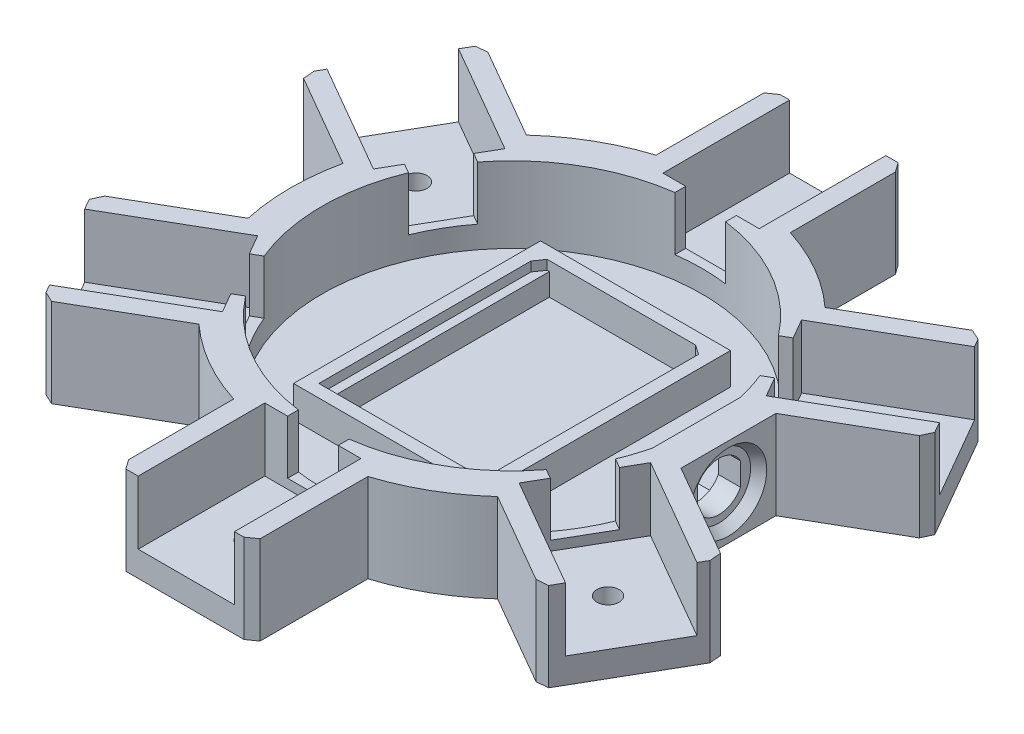
SolidWorks part; units mm, degrees
ref_plane "Front" through (0, 0, 0) normal (0, 0, 1) x (1, 0, 0)
ref_plane "Top" through (0, 0, 0) normal (0, 1, 0) x (1, 0, 0)
ref_plane "Right" through (0, 0, 0) normal (1, 0, 0) x (0, 0, -1)
sketch "Эскиз1" plane through (0, 0, 0) normal (0, 1, 0) x (1, 0, 0)
  line L0 (0, 0) -> (0, 74.8456) construction
  line L1 (63.5176, 45.4476) -> (11.5561, 15.4476) construction
  line L2 (-7.6, 77.7316) -> (7.6, 77.7316) construction
  line L3 (-7.6, 77.7316) -> (-7.6, 17.7316) construction
  line L4 (-7.6, 17.7316) -> (7.6, 17.7316) construction
  line L5 (7.6, 77.7316) -> (7.6, 17.7316) construction
  line L6 (0, 17.7316) -> (0, 77.7316) construction
  line L7 (-7.6, 47.7316) -> (7.6, 47.7316) construction
  line L8 (63.5176, 45.4476) -> (71.1176, 32.284) construction
  line L9 (0, 0) -> (64.8182, 37.4228) construction
  line L10 (71.1176, 32.284) -> (19.1561, 2.284) construction
  line L11 (11.5561, 15.4476) -> (19.1561, 2.284) construction
  line L12 (71.1176, -32.284) -> (19.1561, -2.284) construction
  line L13 (71.1176, -32.284) -> (63.5176, -45.4476) construction
  line L14 (0, 0) -> (64.8182, -37.4228) construction
  line L15 (63.5176, -45.4476) -> (11.5561, -15.4476) construction
  line L16 (19.1561, -2.284) -> (11.5561, -15.4476) construction
  line L17 (7.6, -77.7316) -> (7.6, -17.7316) construction
  line L18 (7.6, -77.7316) -> (-7.6, -77.7316) construction
  line L19 (0, 0) -> (0, -74.8456) construction
  line L20 (-7.6, -77.7316) -> (-7.6, -17.7316) construction
  line L21 (7.6, -17.7316) -> (-7.6, -17.7316) construction
  line L22 (-63.5176, -45.4476) -> (-11.5561, -15.4476) construction
  line L23 (-63.5176, -45.4476) -> (-71.1176, -32.284) construction
  line L24 (0, 0) -> (-64.8182, -37.4228) construction
  line L25 (-71.1176, -32.284) -> (-19.1561, -2.284) construction
  line L26 (-11.5561, -15.4476) -> (-19.1561, -2.284) construction
  line L27 (-71.1176, 32.284) -> (-19.1561, 2.284) construction
  line L28 (-71.1176, 32.284) -> (-63.5176, 45.4476) construction
  line L29 (0, 0) -> (-64.8182, 37.4228) construction
  line L30 (-63.5176, 45.4476) -> (-11.5561, 15.4476) construction
  line L31 (-19.1561, 2.284) -> (-11.5561, 15.4476) construction
  line L32 (0, 31.44) -> (-11.5561, 31.44) construction
  line L33 (-7.6, 31.44) -> (-7.6, 51.44)
  line L34 (-7.6, 51.44) -> (-10.6, 51.44)
  line L35 (-10.6, 51.44) -> (-10.6, 33.3563)
  line L36 (0, 31.44) -> (11.9132, 31.44) construction
  line L38 (7.6, 31.44) -> (7.6, 51.44)
  line L39 (7.6, 51.44) -> (10.6, 51.44)
  line L40 (10.6, 51.44) -> (10.6, 33.3563)
  line L42 (-7.6, 31.44) -> (7.6, 31.44)
  line L43 (39.2483, 34.8999) -> (23.5874, 25.858)
  line L44 (23.4278, 22.3018) -> (40.7483, 32.3018)
  line L45 (40.7483, 32.3018) -> (39.2483, 34.8999)
  line L46 (48.3483, 19.1382) -> (49.8483, 16.5401)
  line L47 (31.0278, 9.1382) -> (48.3483, 19.1382)
  line L48 (49.8483, 16.5401) -> (34.1874, 7.4983)
  line L49 (23.4278, 22.3018) -> (31.0278, 9.1382)
  line L50 (49.8483, -16.5401) -> (34.1874, -7.4983)
  line L51 (31.0278, -9.1382) -> (48.3483, -19.1382)
  line L52 (48.3483, -19.1382) -> (49.8483, -16.5401)
  line L53 (40.7483, -32.3018) -> (39.2483, -34.8999)
  line L54 (23.4278, -22.3018) -> (40.7483, -32.3018)
  line L55 (39.2483, -34.8999) -> (23.5874, -25.858)
  line L56 (31.0278, -9.1382) -> (23.4278, -22.3018)
  line L57 (10.6, -51.44) -> (10.6, -33.3563)
  line L58 (7.6, -31.44) -> (7.6, -51.44)
  line L59 (7.6, -51.44) -> (10.6, -51.44)
  line L60 (-7.6, -51.44) -> (-10.6, -51.44)
  line L61 (-7.6, -31.44) -> (-7.6, -51.44)
  line L62 (-10.6, -51.44) -> (-10.6, -33.3563)
  line L63 (7.6, -31.44) -> (-7.6, -31.44)
  line L64 (-39.2483, -34.8999) -> (-23.5874, -25.858)
  line L65 (-23.4278, -22.3018) -> (-40.7483, -32.3018)
  line L66 (-40.7483, -32.3018) -> (-39.2483, -34.8999)
  line L67 (-48.3483, -19.1382) -> (-49.8483, -16.5401)
  line L68 (-31.0278, -9.1382) -> (-48.3483, -19.1382)
  line L69 (-49.8483, -16.5401) -> (-34.1874, -7.4983)
  line L70 (-23.4278, -22.3018) -> (-31.0278, -9.1382)
  line L71 (-49.8483, 16.5401) -> (-34.1874, 7.4983)
  line L72 (-31.0278, 9.1382) -> (-48.3483, 19.1382)
  line L73 (-48.3483, 19.1382) -> (-49.8483, 16.5401)
  line L74 (-40.7483, 32.3018) -> (-39.2483, 34.8999)
  line L75 (-23.4278, 22.3018) -> (-40.7483, 32.3018)
  line L76 (-39.2483, 34.8999) -> (-23.5874, 25.858)
  line L77 (-31.0278, 9.1382) -> (-23.4278, 22.3018)
  line L78 (34.1874, 7.4983) -> (34.1874, -7.4983)
  line L79 (29.1874, 6.9352) -> (29.1874, -6.9352)
  arc A0 (29.1874, 6.9352) -> (29.1874, -6.9352) centre (0, 0) ccw
  arc A1 (-10.6, 33.3563) -> (-23.5874, 25.858) centre (0, 0) ccw
  arc A2 (-34.1874, 7.4983) -> (-34.1874, -7.4983) centre (0, 0) ccw
  arc A3 (23.5874, 25.858) -> (10.6, 33.3563) centre (0, 0) ccw
  arc A4 (-23.5874, -25.858) -> (-10.6, -33.3563) centre (0, 0) ccw
  arc A5 (10.6, -33.3563) -> (23.5874, -25.858) centre (0, 0) ccw
  point P3 (0, 47.7316)
  dimension "D2" = 60
  dimension "D3" = 70
  dimension "D1" = 15.2
  dimension "D4" = 60
  dimension "D6" = 20
  dimension "D7" = 3
  dimension "D8" = 3
  dimension "D9" = 31.44
  dimension "D10" = 6
  dimension "D11" = 5
  dimension "D5" = 6
extrude "Бобышка-Вытянуть1" add sketch "Эскиз1" along normal blind 12
sketch "Эскиз2" plane through (0, 0, 0) normal (0, -1, 0) x (1, 0, 0)
  line L0 (-10.6, 51.44) -> (10.6, 51.44)
  line L1 (10.6, 51.44) -> (10.6, 33.3563)
  line L2 (-10.6, 51.44) -> (-10.6, 33.3563)
  line L3 (-23.5874, 25.858) -> (-39.2483, 34.8999)
  line L4 (-39.2483, 34.8999) -> (-49.8483, 16.5401)
  line L5 (-49.8483, 16.5401) -> (-34.1874, 7.4983)
  line L6 (-34.1874, -7.4983) -> (-49.8483, -16.5401)
  line L7 (-49.8483, -16.5401) -> (-48.3483, -19.1382)
  line L8 (-48.3483, -19.1382) -> (-39.2483, -34.8999)
  line L9 (-39.2483, -34.8999) -> (-23.5874, -25.858)
  line L10 (-10.6, -33.3563) -> (-10.6, -51.44)
  line L11 (-10.6, -51.44) -> (10.6, -51.44)
  line L12 (10.6, -51.44) -> (10.6, -33.3563)
  line L13 (23.5874, -25.858) -> (39.2483, -34.8999)
  line L14 (39.2483, -34.8999) -> (49.8483, -16.5401)
  line L15 (49.8483, -16.5401) -> (34.1874, -7.4983)
  line L16 (34.1874, -7.4983) -> (34.1874, 7.4983)
  line L17 (34.1874, 7.4983) -> (49.8483, 16.5401)
  line L18 (49.8483, 16.5401) -> (39.2483, 34.8999)
  line L19 (39.2483, 34.8999) -> (23.5874, 25.858)
  arc A0 (-34.1874, 7.4983) -> (-34.1874, -7.4983) centre (0, 0) ccw
  arc A1 (-10.6, 33.3563) -> (-23.5874, 25.858) centre (0, 0) ccw
  arc A2 (23.5874, 25.858) -> (10.6, 33.3563) centre (0, 0) ccw
  arc A3 (-23.5874, -25.858) -> (-10.6, -33.3563) centre (0, 0) ccw
  arc A4 (10.6, -33.3563) -> (23.5874, -25.858) centre (0, 0) ccw
extrude "Бобышка-Вытянуть2" add sketch "Эскиз2" along normal blind 2
sketch "Эскиз3" plane through (0, 0, 0) normal (0, 1, 0) x (1, 0, 0)
  line L0 (0, 31.44) -> (0, 51.44) construction
  line L1 (-7.6, 51.44) -> (7.6, 51.44)
  line L2 (-7.6, 51.44) -> (-7.6, 31.44)
  line L3 (-7.6, 31.44) -> (7.6, 31.44)
  line L4 (7.6, 51.44) -> (7.6, 31.44)
  line L5 (40.7483, 32.3018) -> (48.3483, 19.1382)
  line L6 (40.7483, 32.3018) -> (23.4278, 22.3018)
  line L7 (23.4278, 22.3018) -> (31.0278, 9.1382)
  line L8 (48.3483, 19.1382) -> (31.0278, 9.1382)
  line L9 (27.2278, 15.72) -> (44.5483, 25.72) construction
  line L10 (48.3483, -19.1382) -> (40.7483, -32.3018)
  line L11 (48.3483, -19.1382) -> (31.0278, -9.1382)
  line L12 (31.0278, -9.1382) -> (23.4278, -22.3018)
  line L13 (40.7483, -32.3018) -> (23.4278, -22.3018)
  line L14 (27.2278, -15.72) -> (44.5483, -25.72) construction
  line L15 (7.6, -51.44) -> (-7.6, -51.44)
  line L16 (7.6, -51.44) -> (7.6, -31.44)
  line L17 (7.6, -31.44) -> (-7.6, -31.44)
  line L18 (-7.6, -51.44) -> (-7.6, -31.44)
  line L19 (0, -31.44) -> (0, -51.44) construction
  line L20 (-40.7483, -32.3018) -> (-48.3483, -19.1382)
  line L21 (-40.7483, -32.3018) -> (-23.4278, -22.3018)
  line L22 (-23.4278, -22.3018) -> (-31.0278, -9.1382)
  line L23 (-48.3483, -19.1382) -> (-31.0278, -9.1382)
  line L24 (-27.2278, -15.72) -> (-44.5483, -25.72) construction
  line L25 (-48.3483, 19.1382) -> (-40.7483, 32.3018)
  line L26 (-48.3483, 19.1382) -> (-31.0278, 9.1382)
  line L27 (-31.0278, 9.1382) -> (-23.4278, 22.3018)
  line L28 (-40.7483, 32.3018) -> (-23.4278, 22.3018)
  line L29 (-27.2278, 15.72) -> (-44.5483, 25.72) construction
  circle A0 centre (0, 41.44) radius 1.75
  circle A1 centre (35.8881, 20.72) radius 1.75
  circle A2 centre (35.8881, -20.72) radius 1.75
  circle A3 centre (0, -41.44) radius 1.75
  circle A4 centre (-35.8881, -20.72) radius 1.75
  circle A5 centre (-35.8881, 20.72) radius 1.75
  dimension "D1" = 3.5
  dimension "D2" = 6
extrude "Бобышка-Вытянуть3" add sketch "Эскиз3" along normal blind 2
sketch "Эскиз4" plane through (0, 12, 0) normal (0, 1, 0) x (1, 0, 0)
  line L0 (0, 31.44) -> (0, 28.9927) construction
  line L1 (7.6, 31.44) -> (-7.6, 31.44) construction
  line L2 (25.6064, 19.4027) -> (29.6064, 12.4745)
  line L3 (-4, 31.8771) -> (4, 31.8771)
  line L4 (-4, 31.8771) -> (-4, 28.5556)
  line L5 (-4, 28.5556) -> (4, 28.5556)
  line L6 (4, 31.8771) -> (4, 28.5556)
  line L7 (0, 28.5556) -> (0, 31.8771) construction
  line L8 (-4, 30.2163) -> (4, 30.2163) construction
  line L9 (25.6064, 19.4027) -> (22.7298, 17.7419)
  line L10 (22.7298, 17.7419) -> (26.7298, 10.8137)
  line L11 (29.6064, 12.4745) -> (26.7298, 10.8137)
  line L12 (27.2278, 15.72) -> (25.1084, 14.4963) construction
  line L13 (24.7298, 14.2778) -> (27.6064, 15.9386) construction
  line L14 (24.1681, 18.5723) -> (28.1681, 11.6441) construction
  line L15 (29.6064, -12.4745) -> (25.6064, -19.4027)
  line L16 (29.6064, -12.4745) -> (26.7298, -10.8137)
  line L17 (26.7298, -10.8137) -> (22.7298, -17.7419)
  line L18 (25.6064, -19.4027) -> (22.7298, -17.7419)
  line L19 (27.2278, -15.72) -> (25.1084, -14.4963) construction
  line L20 (24.7298, -14.2778) -> (27.6064, -15.9386) construction
  line L21 (28.1681, -11.6441) -> (24.1681, -18.5723) construction
  line L22 (4, -31.8771) -> (-4, -31.8771)
  line L23 (4, -31.8771) -> (4, -28.5556)
  line L24 (4, -28.5556) -> (-4, -28.5556)
  line L25 (-4, -31.8771) -> (-4, -28.5556)
  line L26 (0, -31.44) -> (0, -28.9927) construction
  line L27 (0, -28.5556) -> (0, -31.8771) construction
  line L28 (4, -30.2163) -> (-4, -30.2163) construction
  line L29 (-25.6064, -19.4027) -> (-29.6064, -12.4745)
  line L30 (-25.6064, -19.4027) -> (-22.7298, -17.7419)
  line L31 (-22.7298, -17.7419) -> (-26.7298, -10.8137)
  line L32 (-29.6064, -12.4745) -> (-26.7298, -10.8137)
  line L33 (-27.2278, -15.72) -> (-25.1084, -14.4963) construction
  line L34 (-24.7298, -14.2778) -> (-27.6064, -15.9386) construction
  line L35 (-24.1681, -18.5723) -> (-28.1681, -11.6441) construction
  line L36 (-29.6064, 12.4745) -> (-25.6064, 19.4027)
  line L37 (-29.6064, 12.4745) -> (-26.7298, 10.8137)
  line L38 (-26.7298, 10.8137) -> (-22.7298, 17.7419)
  line L39 (-25.6064, 19.4027) -> (-22.7298, 17.7419)
  line L40 (-27.2278, 15.72) -> (-25.1084, 14.4963) construction
  line L41 (-24.7298, 14.2778) -> (-27.6064, 15.9386) construction
  line L42 (-28.1681, 11.6441) -> (-24.1681, 18.5723) construction
  point P5 (0, 30.2163)
  point P13 (26.1681, 15.1082)
  point P24 (26.1681, -15.1082)
  point P35 (0, -30.2163)
  point P46 (-26.1681, -15.1082)
  point P57 (-26.1681, 15.1082)
  dimension "D1" = 8
  dimension "D2" = 6
extrude "Вырез-Вытянуть1" cut sketch "Эскиз4" against normal blind 8.5
sketch "Эскиз5" plane through (34.1874, 0, 0) normal (1, 0, 0) x (0, 0, -1)
  line L0 (0, 12) -> (0, -2) construction
  line L1 (-7.4983, 12) -> (7.4983, 12) construction
  line L2 (7.4983, -2) -> (-7.4983, -2) construction
  line L3 (-3.4, 6.8062) -> (-3.4, 3.1938)
  line L4 (3.4, 6.8062) -> (3.4, 3.1938)
  arc A0 (-3.4, 3.1938) -> (3.4, 3.1938) centre (0, 5) ccw
  arc A1 (3.4, 6.8062) -> (-3.4, 6.8062) centre (0, 5) ccw
  dimension "D1" = 7.7
  dimension "D2" = 3.4
  dimension "D3" = 3.4
extrude "Вырез-Вытянуть2" cut sketch "Эскиз5" against normal blind 5
sketch "Эскиз7" plane through (34.1874, 0, 0) normal (1, 0, 0) x (0, 0, -1)
  circle A0 centre (0, 5) radius 5
  dimension "D1" = 10
extrude "Вырез-Вытянуть3" cut sketch "Эскиз7" against normal blind 1.5
chamfer "Фаска1" distance 1.5 angle 35 1 edges at (34.1874, 5, -5)
sketch "Эскиз8" plane through (29.1874, 0, 0) normal (-1, 0, 0) x (0, 0, 1)
  circle A0 centre (0, 5) radius 6.25
  dimension "D1" = 12.5
extrude "Вырез-Вытянуть4" cut sketch "Эскиз8" along normal blind 5
sketch "Эскиз6" plane through (0, 0, 0) normal (0, 1, 0) x (1, 0, 0)
  line L1 (-13, 17.5) -> (13, 17.5)
  line L2 (-13, 17.5) -> (-13, -17.5)
  line L3 (-13, -17.5) -> (13, -17.5)
  line L4 (13, 17.5) -> (13, -17.5)
  line L5 (0, -17.5) -> (0, 17.5) construction
  line L6 (-13, 0) -> (13, 0) construction
  line L7 (-15, 19.5) -> (15, 19.5)
  line L8 (-15, 19.5) -> (-15, -19.5)
  line L9 (-15, -19.5) -> (15, -19.5)
  line L10 (15, 19.5) -> (15, -19.5)
  line L11 (0, -19.5) -> (0, 19.5) construction
  line L12 (-15, 0) -> (15, 0) construction
  point P0 (0, 0)
  point P4 (0, 0)
  dimension "D1" = 26
  dimension "D2" = 35
  dimension "D3" = 0
  dimension "D4" = 0
  dimension "D5" = 2
  dimension "D6" = 2
extrude "Бобышка-Вытянуть4" add sketch "Эскиз6" along normal blind 5
sketch "Эскиз9" plane through (0, 0, 0) normal (0, 1, 0) x (1, 0, 0)
  line L0 (-13, -17.5) -> (13, -17.5) construction
  line L1 (-13, 17.5) -> (-11.6, 17.5)
  line L2 (-13, 17.5) -> (-13, -17.5)
  line L3 (-13, -17.5) -> (-11.6, -17.5)
  line L4 (-11.6, 17.5) -> (-11.6, -16.1)
  line L5 (-13, -17.5) -> (13, -17.5) construction
  line L6 (13, 17.5) -> (11.6, 17.5)
  line L7 (13, 17.5) -> (13, -17.5)
  line L8 (13, -17.5) -> (11.6, -17.5)
  line L9 (11.6, 17.5) -> (11.6, -16.1)
  line L11 (-11.6, -17.5) -> (11.6, -17.5)
  line L13 (-11.6, -16.1) -> (11.6, -16.1)
  dimension "D1" = 1.4
  dimension "D2" = 1.4
  dimension "D3" = 1.4
extrude "Бобышка-Вытянуть5" add sketch "Эскиз9" along normal blind 3.5
chamfer "Фаска2" distance 1.5 angle 35 2 edges at (13, 4.25, -17.5) (-13, 4.25, -17.5)
sketch "Эскиз10" plane through (0, 0, 0) normal (0, 1, 0) x (1, 0, 0)
  circle A0 centre (0, 41.44) radius 1.75
  circle A1 centre (35.8881, 20.72) radius 1.75
  circle A2 centre (35.8881, -20.72) radius 1.75
  circle A3 centre (0, -41.44) radius 1.75
  circle A4 centre (-35.8881, -20.72) radius 1.75
  circle A5 centre (-35.8881, 20.72) radius 1.75
  dimension "D1" = 6
extrude "Вырез-Вытянуть5" cut sketch "Эскиз10" against normal through all
chamfer "Фаска3" distance 1.5 angle 35 12 edges at (-49.8483, 5, -16.5401) (-39.2483, 5, -34.8999) (39.2483, 5, 34.8999) (10.6, 5, 51.44) (-10.6, 5, 51.44) (-49.8483, 5, 16.5401) (-39.2483, 5, 34.8999) (49.8483, 5, 16.5401) (49.8483, 5, -16.5401) (39.2483, 5, -34.8999) (10.6, 5, -51.44) (-10.6, 5, -51.44)
